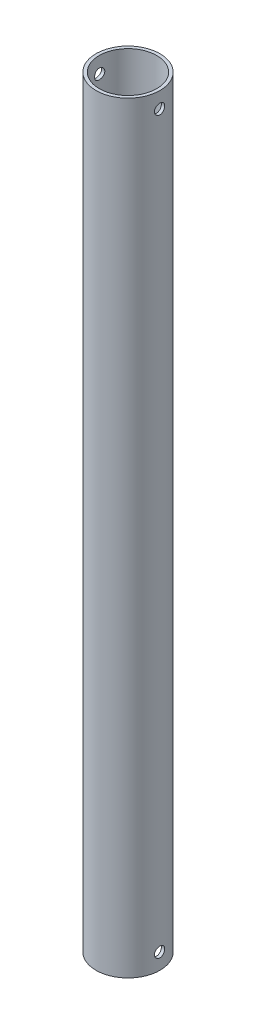
SolidWorks part; units mm, degrees
material "Toray T700"
ref_plane "Front" through (0, 0, 0) normal (0, 0, 1) x (1, 0, 0)
ref_plane "Top" through (0, 0, 0) normal (0, 1, 0) x (1, 0, 0)
ref_plane "Right" through (0, 0, 0) normal (1, 0, 0) x (0, 0, -1)
sketch "Sketch1" plane through (0, 0, 0) normal (0, 1, 0) x (1, 0, 0)
  line L5 (4.7969, 0) -> (-5.97, 0) construction
  circle A0 centre (0, 0) radius 10
  circle A1 centre (0, 0) radius 9
  dimension "D1" = 20
  dimension "D2" = 18
extrude "Boss-Extrude1" add sketch "Sketch1" along normal blind 238.5
ref_axis "Axis1" through (0, 238.5, 0) along (0, -1, 0)
ref_plane "Plane1" through (-10, 0, 0) normal (-1, 0, 0) x (0, 0, 1)
hole_wizard "M3 Clearance Hole1" positions "Sketch3" profile "Sketch2" hole size "M3" standard "DIN" end condition through all
sketch "Sketch3" plane through (-10, 0, 0) normal (-1, 0, 0) x (0, 0, 1)
  line L0 (-9, 0) -> (9, 0) construction
  line L1 (0, -50) -> (0, 50) construction
  point P0 (0, 5)
  dimension "D1" = 5
sketch "Sketch2" plane through (-10, 5, 0) normal (0, 1, 0) x (0, 0, 1)
  line L0 (0, 0) -> (0, 20)
  line L1 (0, 20) -> (1.6, 20)
  line L2 (1.6, 20) -> (1.6, 0)
  line L5 (1.6, 0) -> (0, 0)
  line L11 (0, -6.35) -> (0, 107.95) construction
  dimension "Thru Hole Dia." = 3.2
  dimension "Thru Hole Depth" = 20
ref_plane "Plane2" through (0, 119.25, 0) normal (0, 1, 0) x (1, 0, 0)
mirror "Mirror1" about plane through (0, 119.25, 0) normal (0, 1, 0) of "M3 Clearance Hole1"
